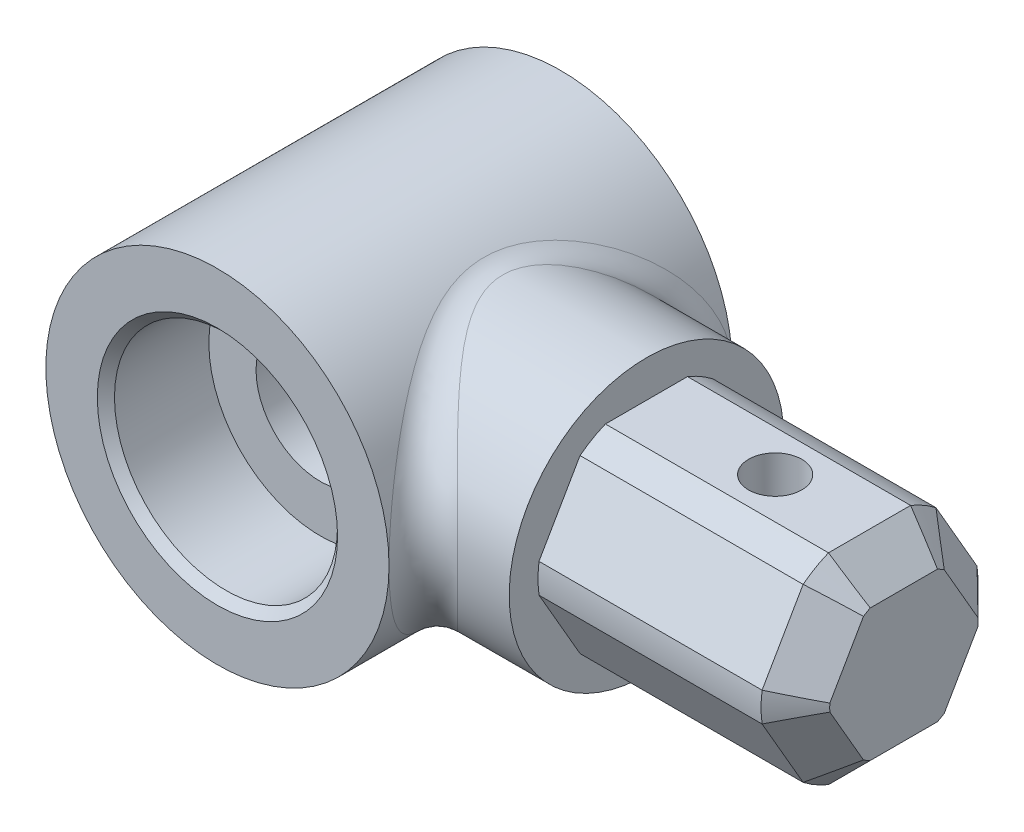
SolidWorks part; units mm, degrees
ref_plane "Front Plane" through (0, 0, 0) normal (0, 0, 1) x (1, 0, 0)
ref_plane "Top Plane" through (0, 0, 0) normal (0, 1, 0) x (1, 0, 0)
ref_plane "Right Plane" through (0, 0, 0) normal (1, 0, 0) x (0, 0, -1)
sketch "Sketch2" plane through (0, 0, 0) normal (0, 0, 1) x (1, 0, 0)
  circle A0 centre (0, 0) radius 10
  dimension "D1" = 20
extrude "Boss-Extrude1" add sketch "Sketch2" along normal blind 20
sketch "Sketch3" plane through (0, 0, 0) normal (1, 0, 0) x (0, 0, -1)
  line L0 (0, -10) -> (0, 10) construction
  line L1 (-20, 10) -> (-20, -10) construction
  line L2 (0, -10) -> (0, 10)
  line L3 (-20, 10) -> (-20, -10)
  line L4 (0, 0) -> (-20, 0) construction
  circle A0 centre (-10, 0) radius 8
  dimension "D1" = 16
extrude "Boss-Extrude2" add sketch "Sketch3" along normal blind 15 contours A0
sketch "Sketch4" plane through (15, 0, 0) normal (1, 0, 0) x (0, 0, -1)
  line L1 (-3.245, 0) -> (-6.6225, 5.85)
  line L2 (-6.6225, 5.85) -> (-13.3775, 5.85)
  line L3 (-13.3775, 5.85) -> (-16.755, 0)
  line L4 (-16.755, 0) -> (-13.3775, -5.85)
  line L5 (-13.3775, -5.85) -> (-6.6225, -5.85)
  line L6 (-6.6225, -5.85) -> (-3.245, 0)
  circle A0 centre (-10, 0) radius 6.32
  circle A1 centre (-10, 0) radius 5.85 construction
  dimension "D1" = 12.64
  dimension "D2" = 11.7
extrude "Boss-Extrude3" add sketch "Sketch4" along normal blind 15 contours L5 L6 L1 L2 L3 L4 region at (15, 0, 10)
fillet "Fillet1" radius 2 1 edges at (9.956, 0.9372, 2.0551)
chamfer "Chamfer1" distance 2 angle 45 12 edges at (30, -2.925, 15.0662) (30, 2.925, 15.0662) (30, 5.85, 10) (30, 2.925, 4.9338) (30, -2.925, 4.9338) (30, -5.85, 10) (30, 0, 3.68) (30, -5.4733, 6.84) (30, -5.4733, 13.16) (30, 0, 16.32) (30, 5.4733, 13.16) (30, 5.4733, 6.84)
ref_point "MountPoint (FreeJoint)"
ref_axis "Axis1" through (15, 0, 10) along (-1, 0, 0)
sketch "Sketch5" plane through (0, 5.85, 15) normal (0, -1, 0) x (1, 0, 0)
  line L1 (15, -7.3916) -> (15, -2.6084) construction
  circle A0 centre (22.5, -5) radius 1.55
  dimension "D1" = 3.1
  dimension "D2" = 7.5
extrude "Cut-Extrude1" cut sketch "Sketch5" along normal up to next
sketch "Sketch6" plane through (0, 0, 0) normal (0, 0, -1) x (-1, 0, 0)
  circle A0 centre (0, 0) radius 3.75
  dimension "D1" = 7.5
extrude "Cut-Extrude2" cut sketch "Sketch6" against normal up to next
sketch "Sketch7" plane through (0, 0, 0) normal (0, 0, -1) x (-1, 0, 0)
  circle A0 centre (0, 0) radius 6.5
  dimension "D1" = 13
extrude "Cut-Extrude3" cut sketch "Sketch7" against normal blind 6
sketch "Sketch8" plane through (0, 0, 20) normal (0, 0, 1) x (1, 0, 0)
  circle A0 centre (0, 0) radius 6.5 construction
  circle A1 centre (0, 0) radius 6.5
extrude "Cut-Extrude4" cut sketch "Sketch8" against normal blind 6
chamfer "Chamfer2" distance 0.5 angle 45 2 edges at (6.5, 0, 20) (-6.5, 0, 0)
